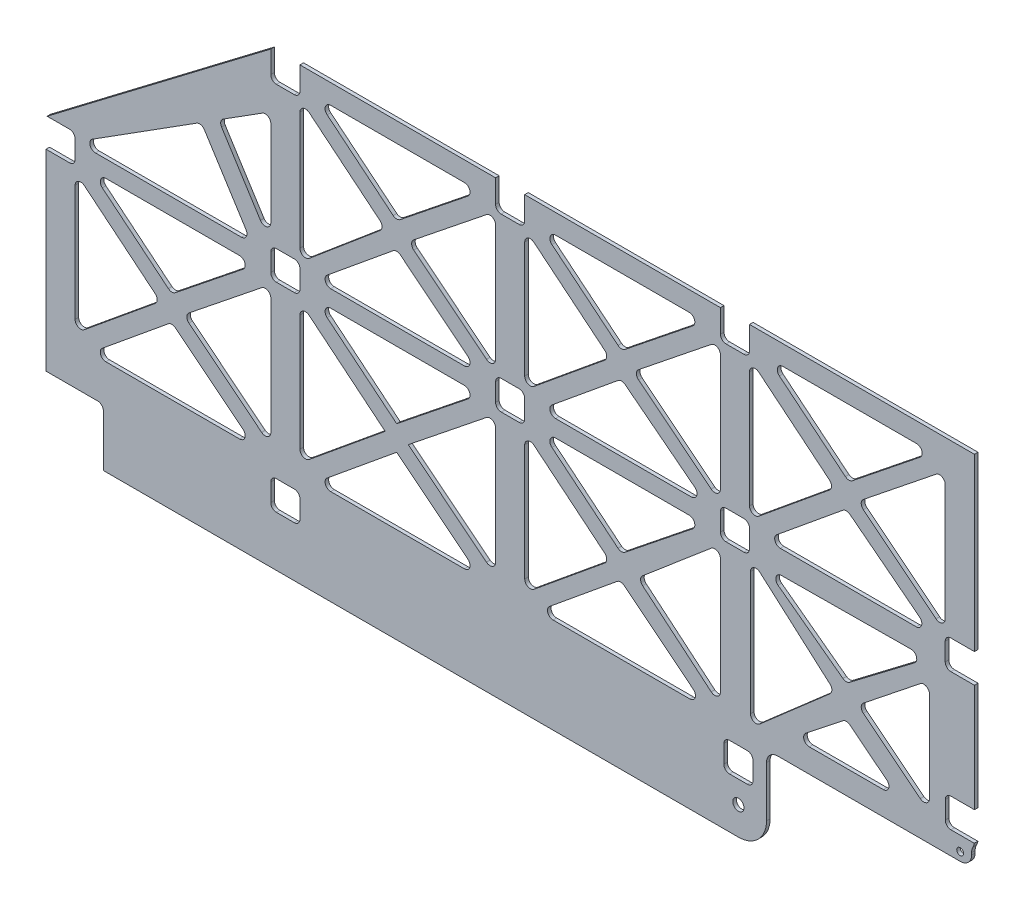
SolidWorks part; units mm, degrees
note: The reader was unsure of these and kept them because the rebuilt part matched: thickness of "Brida base1", "Chapa metálica1", "Chapa metálica23", "Chapa metálica27", "Chapa metálica32", "Chapa metálica33", "Chapa metálica34", "Chapa metálica35", "Chapa metálica36", "Chapa metálica37", "Chapa metálica38", "Chapa metálica39", "Chapa metálica40", "Chapa metálica41", "Chapa metálica42", "Chapa metálica43", "Chapa metálica44", "Chapa metálica45", "Chapa metálica46", "Chapa metálica47", "Chapa metálica48", "Chapa metálica49", "Chapa metálica50", "Chapa metálica51", "Chapa metálica52", "Chapa metálica53", "Chapa metálica54", "Chapa metálica55", "Chapa metálica56", "Chapa metálica57", "Chapa metálica58".
other "Elemento de detalle13"
other "Elemento de detalle19"
other "Carpeta de soldadura"
material "ASTM A36 Acero"
ref_plane "Alzado" through (0, 0, 0) normal (0, 0, 1) x (1, 0, 0)
ref_plane "Planta" through (0, 0, 0) normal (0, 1, 0) x (1, 0, 0)
ref_plane "Vista lateral" through (0, 0, 0) normal (1, 0, 0) x (0, 0, -1)
sketch "Croquis1" plane through (0, 0, 0) normal (0, 0, 1) x (1, 0, 0)
  line L1 (-634.7218, 129.9029) -> (1017.2782, 129.9029)
  line L2 (-634.7218, 129.9029) -> (-634.7218, -670.0971)
  line L3 (-634.7218, -670.0971) -> (1017.2782, -670.0971)
  line L4 (1017.2782, 129.9029) -> (1017.2782, -670.0971)
  dimension "D1" = 800
  dimension "D2" = 1652
base flange "Brida base1" sketch "Croquis1" thickness 6.35 reverse thickness direction no parameters "D1"=0.7366
ref_plane "Plano1" through (0, 0, 0) normal (0, 1, 0) x (1, 0, 0)
sketch "Croquis14" plane through (0, 0, -6.35) normal (0, 0, 1) x (1, 0, 0)
  line L0 (-634.7218, 129.9029) -> (-634.7218, -670.0971) construction
  line L1 (-634.7218, -670.0971) -> (1017.2782, -670.0971) construction
  line L2 (-634.7218, -174.1971) -> (-582.9218, -174.1971)
  line L3 (965.2782, -174.1971) -> (1028.4048, -174.1971)
  line L4 (-451.2573, -29.958) -> (-582.9218, -29.958) construction
  line L5 (-634.7218, -174.1971) -> (-634.7218, -225.9971)
  line L6 (-634.7218, -225.9971) -> (-582.9218, -225.9971)
  line L7 (-582.9218, -174.1971) -> (-582.9218, -225.9971)
  line L8 (1017.2782, 129.9029) -> (-634.7218, 129.9029) construction
  line L9 (-234.7218, -174.1971) -> (-182.9218, -174.1971)
  line L10 (-234.7218, -174.1971) -> (-234.7218, -225.9971)
  line L11 (1017.2782, 129.9029) -> (-634.7218, 129.9029) construction
  line L12 (-234.7218, -225.9971) -> (-182.9218, -225.9971)
  line L13 (-410.7218, 129.9029) -> (-410.7218, -670.0971) construction
  line L14 (-182.9218, -174.1971) -> (-182.9218, -225.9971)
  line L15 (165.2782, -174.1971) -> (217.0782, -174.1971)
  line L16 (165.2782, -174.1971) -> (165.2782, -225.9971)
  line L17 (165.2782, -225.9971) -> (217.0782, -225.9971)
  line L18 (217.0782, -174.1971) -> (217.0782, -225.9971)
  line L19 (565.2782, -174.1971) -> (617.0782, -174.1971)
  line L20 (565.2782, -174.1971) -> (565.2782, -225.9971)
  line L21 (565.2782, -225.9971) -> (617.0782, -225.9971)
  line L22 (617.0782, -174.1971) -> (617.0782, -225.9971)
  line L23 (165.2782, 130.8029) -> (217.0782, 130.8029)
  line L24 (589.2782, 129.9029) -> (589.2782, -670.0971) construction
  line L25 (89.2782, 129.9029) -> (89.2782, -670.0971) construction
  line L26 (565.2782, 130.8029) -> (617.0782, 130.8029)
  line L27 (565.2782, 130.8029) -> (565.2782, 79.0029)
  line L28 (565.2782, 79.0029) -> (617.0782, 79.0029)
  line L29 (617.0782, 130.8029) -> (617.0782, 79.0029)
  line L30 (-582.9218, 78.1029) -> (-582.9218, -138.0188) construction
  line L31 (-582.9218, -138.0188) -> (-451.2573, -29.958) construction
  line L32 (-451.2573, -29.958) -> (-582.9218, 78.1029) construction
  line L33 (789.2782, -227.6711) -> (789.2782, -337.0198) construction
  line L34 (809.8215, -360.2316) -> (937.2192, -360.2316) construction
  line L35 (417.7527, -360.2316) -> (789.2782, -360.2316) construction
  line L36 (-234.7218, 31.6626) -> (-234.7218, -174.0284)
  line L37 (-234.7218, -174.0284) -> (-327.6777, -27.1786)
  line L38 (965.2782, -174.1971) -> (965.2782, -225.9971)
  line L39 (215.2782, -200.0989) -> (315.2782, -200.0989) construction
  line L40 (617.0782, 78.1029) -> (617.0782, -170.9006)
  line L41 (965.2782, -225.9971) -> (1028.4048, -225.9971)
  line L42 (1028.4048, -174.1971) -> (1028.4048, -225.9971)
  line L43 (-634.7218, 129.9029) -> (-634.7218, -670.0971) construction
  line L44 (768.7748, -46.3989) -> (617.0782, 78.1029)
  line L45 (617.0782, -170.9006) -> (768.7748, -46.3989)
  line L46 (789.2782, -68.3814) -> (643.8962, -187.7006)
  line L47 (942.9042, -187.7006) -> (789.2782, -68.3814)
  line L48 (643.8962, -187.7006) -> (942.9042, -187.7006)
  line L49 (-327.6777, -27.1786) -> (-234.7218, 31.6626)
  line L50 (-268.9149, -187.7006) -> (-358.2681, -46.5423)
  line L51 (-358.2681, -46.5423) -> (-581.2671, -187.7006)
  line L52 (-234.7218, 79.0029) -> (-634.7218, -174.1971) construction
  line L53 (-634.7218, -174.1971) -> (-631.748, -174.0915) construction
  line L54 (937.2192, -258.7052) -> (937.2192, -461.7581)
  line L55 (-581.2671, -187.7006) -> (-268.9149, -187.7006)
  line L56 (694.6653, -467.8409) -> (883.8912, -467.8409)
  line L58 (789.2782, -467.8409) -> (789.2782, -392.9074) construction
  line L59 (789.2782, -68.3814) -> (789.2782, -360.2316) construction
  line L84 (165.2782, 130.8029) -> (165.2782, 79.0029)
  line L85 (165.2782, 79.0029) -> (217.0782, 79.0029)
  line L86 (217.0782, 130.8029) -> (217.0782, 79.0029)
  line L87 (-234.7218, 130.8029) -> (-182.9218, 130.8029)
  line L88 (-234.7218, 130.8029) -> (-234.7218, 79.0029)
  line L89 (-234.7218, 79.0029) -> (-182.9218, 79.0029)
  line L90 (-182.9218, 130.8029) -> (-182.9218, 79.0029)
  line L91 (-634.7218, 130.8029) -> (-582.9218, 130.8029)
  line L92 (-634.7218, 130.8029) -> (-634.7218, 79.0029)
  line L93 (-634.7218, 79.0029) -> (-582.9218, 79.0029)
  line L94 (-582.9218, 130.8029) -> (-582.9218, 79.0029)
  line L95 (-182.9218, 78.1029) -> (-182.9218, -174.0284)
  line L96 (-182.9218, -174.0284) -> (-31.2252, -46.3989)
  line L97 (-31.2252, -46.3989) -> (-182.9218, 78.1029)
  line L98 (-156.1038, 94.9029) -> (138.2639, 94.9029)
  line L99 (138.2639, 94.9029) -> (-10.7218, -24.4164)
  line L100 (-10.7218, -24.4164) -> (-156.1038, 94.9029)
  line L101 (165.2782, 78.1029) -> (165.2782, -170.9006)
  line L102 (165.2782, -170.9006) -> (9.8215, -46.3989)
  line L103 (9.8215, -46.3989) -> (165.2782, 78.1029)
  line L104 (-10.7218, -68.3814) -> (-156.1038, -187.7006)
  line L105 (138.2639, -187.7006) -> (-10.7218, -68.3814)
  line L106 (-156.1038, -187.7006) -> (138.2639, -187.7006)
  line L107 (-31.2252, -46.3989) -> (-182.9218, -46.3989) construction
  line L108 (217.0782, 78.1029) -> (217.0782, -170.9006)
  line L109 (217.0782, -170.9006) -> (368.7748, -46.3989)
  line L110 (368.7748, -46.3989) -> (217.0782, 78.1029)
  line L111 (243.8962, 94.9029) -> (538.2639, 94.9029)
  line L112 (538.2639, 94.9029) -> (389.2782, -24.4164)
  line L113 (389.2782, -24.4164) -> (243.8962, 94.9029)
  line L114 (565.2782, 78.1029) -> (565.2782, -170.9006)
  line L115 (565.2782, -170.9006) -> (409.8215, -46.3989)
  line L116 (409.8215, -46.3989) -> (565.2782, 78.1029)
  line L117 (389.2782, -68.3814) -> (243.8962, -187.7006)
  line L118 (542.9042, -187.7006) -> (389.2782, -68.3814)
  line L119 (243.8962, -187.7006) -> (542.9042, -187.7006)
  line L120 (368.7748, -46.3989) -> (217.0782, -46.3989) construction
  line L124 (648.5365, 94.9029) -> (942.9042, 94.9029)
  line L125 (942.9042, 94.9029) -> (793.9185, -24.4164)
  line L126 (793.9185, -24.4164) -> (648.5365, 94.9029)
  line L127 (965.2782, 78.1029) -> (965.2782, -170.9006)
  line L128 (965.2782, -170.9006) -> (809.8215, -46.3989)
  line L129 (809.8215, -46.3989) -> (965.2782, 78.1029)
  line L134 (-182.9218, -234.5006) -> (-182.9218, -483.5041)
  line L135 (-182.9218, -483.5041) -> (-31.2252, -359.0024)
  line L136 (-31.2252, -359.0024) -> (-182.9218, -234.5006)
  line L137 (-156.1038, -217.7006) -> (138.2639, -217.7006)
  line L138 (138.2639, -217.7006) -> (-10.7218, -337.0198)
  line L139 (-10.7218, -337.0198) -> (-156.1038, -217.7006)
  line L140 (165.2782, -234.5006) -> (165.2782, -483.5041)
  line L141 (165.2782, -483.5041) -> (9.8215, -359.0024)
  line L142 (9.8215, -359.0024) -> (165.2782, -234.5006)
  line L143 (-10.7218, -380.9849) -> (-156.1038, -500.3041)
  line L144 (138.2639, -500.3041) -> (-10.7218, -380.9849)
  line L145 (-156.1038, -500.3041) -> (138.2639, -500.3041)
  line L146 (-31.2252, -359.0024) -> (-182.9218, -359.0024) construction
  line L147 (217.0782, -234.5006) -> (217.0782, -483.5041)
  line L148 (217.0782, -483.5041) -> (368.7748, -359.0024)
  line L149 (368.7748, -359.0024) -> (217.0782, -234.5006)
  line L150 (243.8962, -217.7006) -> (538.2639, -217.7006)
  line L151 (538.2639, -217.7006) -> (389.2782, -337.0198)
  line L152 (389.2782, -337.0198) -> (243.8962, -217.7006)
  line L153 (565.2782, -235.1156) -> (565.2782, -484.1191)
  line L154 (565.2782, -484.1191) -> (417.7527, -360.2316)
  line L155 (417.7527, -360.2316) -> (565.2782, -235.1156)
  line L156 (387.6729, -378.8043) -> (239.634, -500.3041)
  line L157 (539.3812, -500.3041) -> (387.6729, -378.8043)
  line L158 (239.634, -500.3041) -> (539.3812, -500.3041)
  line L159 (368.7748, -359.0024) -> (217.0782, -359.0024) construction
  line L160 (618.7236, -228.0512) -> (618.7236, -491.1834)
  line L161 (618.7236, -491.1834) -> (768.7748, -360.2316)
  line L162 (768.7748, -360.2316) -> (618.7236, -228.0512)
  line L163 (643.8962, -228.8118) -> (934.6603, -226.5304)
  line L164 (934.6603, -226.5304) -> (789.2782, -337.0198)
  line L165 (789.2782, -337.0198) -> (643.8962, -228.8118)
  line L167 (937.2192, -461.7581) -> (809.8215, -360.2316)
  line L168 (809.8215, -360.2316) -> (937.2192, -258.7052)
  line L169 (789.2782, -392.9074) -> (694.6653, -467.8409)
  line L170 (883.8912, -467.8409) -> (789.2782, -392.9074)
  line L172 (768.7748, -360.2316) -> (615.7337, -360.2316) construction
  line L173 (-582.9218, -234.5006) -> (-582.9218, -483.5041)
  line L174 (-582.9218, -483.5041) -> (-431.2252, -359.0024)
  line L175 (-431.2252, -359.0024) -> (-582.9218, -234.5006)
  line L176 (-556.1038, -217.7006) -> (-261.7361, -217.7006)
  line L177 (-261.7361, -217.7006) -> (-410.7218, -337.0198)
  line L178 (-410.7218, -337.0198) -> (-556.1038, -217.7006)
  line L179 (-234.7218, -234.5006) -> (-234.7218, -483.5041)
  line L180 (-234.7218, -483.5041) -> (-390.1785, -359.0024)
  line L181 (-390.1785, -359.0024) -> (-234.7218, -234.5006)
  line L182 (-410.7218, -380.9849) -> (-556.1038, -500.3041)
  line L183 (-261.7361, -500.3041) -> (-410.7218, -380.9849)
  line L184 (-556.1038, -500.3041) -> (-261.7361, -500.3041)
  line L185 (-431.2252, -359.0024) -> (-582.9218, -359.0024) construction
  dimension "D21" = 30
  dimension "D3" = 0
  dimension "D4" = 2
  dimension "D5" = 51.8
  dimension "D6" = 51.8
  dimension "D7" = 51.8
  dimension "D8" = 304.1
  dimension "D9" = 2
  dimension "D10" = 2
  dimension "D11" = 2
  dimension "D12" = 4
  dimension "D13" = 2
  dimension "D14" = 224
  dimension "D15" = 40
  dimension "D16" = 400
  dimension "D18" = 400
  dimension "D19" = 400
  dimension "D29" = 1000
extrude "Cortar-Extruir1" cut sketch "Croquis14" along normal through all
ref_plane "Plano5" through (0, -200.0971, 0) normal (0, 1, 0) x (1, 0, 0)
ref_plane "Plano6" through (0, -40.0971, 0) normal (0, 1, 0) x (1, 0, 0)
ref_plane "Plano3" through (0, -420.0971, 0) normal (0, -1, 0) x (-1, 0, 0)
fillet "Redondeo1" radius 10 61 edges at (618.7236, -491.1834, -3.175) (617.0782, -225.9971, -3.175) (643.8962, -228.8118, -3.175) (934.6603, -226.5304, -3.175) (789.2782, -337.0198, -3.175) (789.2782, -392.9074, -3.175) (809.8215, -360.2316, -3.175) (-234.7218, -234.5006, -3.175) (-261.7361, -217.7006, -3.175) (-390.1785, -359.0024, -3.175) (-410.7218, -337.0198, -3.175) (-410.7218, -380.9849, -3.175) (-182.9218, -234.5006, -3.175) (243.8962, 94.9029, -3.175) (138.2639, -187.7006, -3.175) (-156.1038, -217.7006, -3.175) (-156.1038, -187.7006, -3.175) (-31.2252, -46.3989, -3.175) (-10.7218, -24.4164, -3.175) (-10.7218, -68.3814, -3.175) (165.2782, 78.1029, -3.175) (-182.9218, -483.5041, -3.175) (-261.7361, -500.3041, -3.175) (-156.1038, -500.3041, -3.175) (138.2639, -500.3041, -3.175) (243.8962, -217.7006, -3.175) (217.0782, -483.5041, -3.175) (565.2782, -484.1191, -3.175) (539.3812, -500.3041, -3.175) (368.7748, -359.0024, -3.175) (389.2782, -337.0198, -3.175) (387.6729, -378.8043, -3.175) (565.2782, -235.1156, -3.175) (538.2639, -217.7006, -3.175) (565.2782, -170.9006, -3.175) (243.8962, -187.7006, -3.175) (542.9042, -187.7006, -3.175) (368.7748, -46.3989, -3.175) (389.2782, -24.4164, -3.175) (409.8215, -46.3989, -3.175) (538.2639, 94.9029, -3.175) (565.2782, 78.1029, -3.175) (809.8215, -46.3989, -3.175) (965.2782, 78.1029, -3.175) (942.9042, 94.9029, -3.175) (-182.9218, 78.1029, -3.175) (617.0782, -170.9006, -3.175) (768.7748, -46.3989, -3.175) (789.2782, -68.3814, -3.175) (942.9042, -187.7006, -3.175) (643.8962, -187.7006, -3.175) (617.0782, -174.1971, -3.175) (565.2782, -174.1971, -3.175) (-581.2671, -187.7006, -3.175) (-268.9149, -187.7006, -3.175) (-234.7218, -174.0284, -3.175) (-327.6777, -27.1786, -3.175) (937.2192, -461.7581, -3.175) (937.2192, -258.7052, -3.175) (883.8912, -467.8409, -3.175) (694.6653, -467.8409, -3.175)
ref_plane "Plano7" through (0, -476.0971, 0) normal (0, -1, 0) x (-1, 0, 0)
ref_plane "Plano8" through (-410.7218, 0, 0) normal (-1, 0, 0) x (0, 0, 1)
ref_plane "Plano9" through (89.2782, 0, 0) normal (-1, 0, 0) x (0, 0, 1)
ref_plane "Plano10" through (591.1782, 0, 0) normal (-1, 0, 0) x (0, 0, 1)
fillet "Redondeo2" radius 10 18 edges at (-182.9218, -174.1971, -3.175) (-234.7218, -174.1971, -3.175) (-234.7218, -225.9971, -3.175) (165.2782, -225.9971, -3.175) (217.0782, -174.1971, -3.175) (165.2782, -174.1971, -3.175) (217.0782, -225.9971, -3.175) (-182.9218, -225.9971, -3.175) (-582.9218, -225.9971, -3.175) (-582.9218, -174.1971, -3.175) (-182.9218, 79.0029, -3.175) (-234.7218, 79.0029, -3.175) (217.0782, 79.0029, -3.175) (165.2782, 79.0029, -3.175) (617.0782, 79.0029, -3.175) (565.2782, 79.0029, -3.175) (965.2782, -225.9971, -3.175) (965.2782, -174.1971, -3.175)
ref_plane "Plano11" through (0, 104.0029, 0) normal (0, 1, 0) x (1, 0, 0)
sketch "Croquis15" plane through (0, 0, -6.35) normal (0, 0, -1) x (-1, 0, 0)
  line L0 (234.7218, 129.9029) -> (634.7218, -174.1971) construction
  line L1 (634.7218, -174.1971) -> (723.5953, -174.1971)
  line L2 (723.5953, -174.1971) -> (723.5953, 159.8909)
  line L3 (723.5953, 159.8909) -> (234.7218, 159.8909)
  line L4 (234.7218, 159.8909) -> (234.7218, 129.9029)
  line L5 (234.7218, 129.9029) -> (234.7218, 128.3578)
  line L6 (234.7218, 129.9029) -> (234.7218, 89.0029) construction
  line L7 (234.7218, 128.3578) -> (632.6894, -174.1971)
  line L9 (632.6894, -174.1971) -> (634.7218, -174.1971)
  line L10 (234.7218, 129.9029) -> (634.7218, 129.9029) construction
  dimension "D1" = 1.23
extrude "Cortar-Extruir2" cut sketch "Croquis15" against normal blind 10 contours L0 L5 L7 L9 | L4 L0 L1 L2 L3 normal cut yes
sketch "Croquis19" plane through (0, 0, 0) normal (0, 0, 1) x (1, 0, 0)
  line L1 (1017.2782, -670.0971) -> (647.2782, -670.0971)
  line L2 (1017.2782, -670.0971) -> (1017.2782, -510.0971)
  line L3 (1017.2782, -510.0971) -> (647.2782, -510.0971)
  line L4 (647.2782, -670.0971) -> (647.2782, -510.0971)
  line L5 (1017.2782, -510.0971) -> (1012.2782, -510.0971)
  line L6 (1017.2782, -510.0971) -> (1017.2782, -480.0971)
  line L7 (1017.2782, -480.0971) -> (1012.2782, -480.0971)
  line L9 (1012.2782, -510.0971) -> (1012.2782, -480.0971)
  dimension "D1" = 160
  dimension "D2" = 370
  dimension "D3" = 30
  dimension "D4" = 5
extrude "Cortar-Extruir3" cut sketch "Croquis19" against normal blind 10 contours L4 L1 L2 L3 | L5 L9 L7 L6 normal cut yes
fillet "Redondeo4" radius 50 1 edges at (647.2782, -670.0971, -3.175)
fillet "Redondeo5" radius 20 3 edges at (647.2782, -510.0971, -3.175) (1017.2782, -480.0971, -3.175)
fillet "Redondeo6" radius 50 1 edges at (-634.7218, -670.0971, -3.175)
fillet "Redondeo7" radius 20 1 edges at (1012.2782, -480.0971, -3.175)
sketch "Croquis20" plane through (0, 0, 0) normal (0, 0, 1) x (1, 0, 0)
  line L0 (966.4782, -510.0971) -> (966.4782, -495.0971) construction
  line L1 (992.2782, -510.0971) -> (667.2782, -510.0971) construction
  line L2 (966.4782, -495.0971) -> (1017.2782, -495.0971) construction
  line L3 (597.2782, -670.0971) -> (597.2782, -620.0971) construction
  line L4 (597.2782, -620.0971) -> (632.6336, -655.4525) construction
  line L5 (1017.2782, -466.8684) -> (1017.2782, -225.9971) construction
  line L7 (991.8782, -488.9971) -> (991.8782, -501.1971) construction
  arc A2 (597.2782, -670.0971) -> (647.2782, -620.0971) centre (597.2782, -620.0971) ccw construction
  circle A3 centre (597.2782, -620.0971) radius 10
  circle A5 centre (991.8782, -495.0971) radius 6.1
  dimension "D1" = 20
  dimension "D4" = 12.2
  dimension "D2" = 45
  dimension "D3" = 15
  dimension "D5" = 20.4
extrude "Cortar-Extruir4" cut sketch "Croquis20" against normal blind 10 normal cut yes
sketch "Croquis21" plane through (0, 0, 0) normal (0, 0, 1) x (1, 0, 0)
  line L0 (-584.7218, -670.0971) -> (597.2782, -670.0971) construction
  line L1 (571.3782, -528.7971) -> (623.1782, -528.7971)
  line L2 (571.3782, -528.7971) -> (571.3782, -580.5971)
  line L3 (571.3782, -580.5971) -> (623.1782, -580.5971)
  line L4 (623.1782, -528.7971) -> (623.1782, -580.5971)
  line L5 (647.2782, -530.0971) -> (647.2782, -620.0971) construction
  line L6 (1017.2782, -466.8684) -> (1017.2782, -225.9971) construction
  line L7 (1017.2782, -469.6371) -> (965.4782, -469.6371)
  line L8 (1017.2782, -469.6371) -> (1017.2782, -417.8371)
  line L9 (1017.2782, -417.8371) -> (965.4782, -417.8371)
  line L11 (965.4782, -469.6371) -> (965.4782, -417.8371)
  line L12 (992.2782, -510.0971) -> (667.2782, -510.0971) construction
  line L13 (-234.7218, -528.7971) -> (-182.9218, -528.7971)
  line L14 (-234.7218, -528.7971) -> (-234.7218, -580.5971)
  line L15 (-234.7218, -580.5971) -> (-182.9218, -580.5971)
  line L16 (-182.9218, -528.7971) -> (-182.9218, -580.5971)
  line L17 (-208.8218, -528.7971) -> (-208.8218, -225.9971) construction
  line L18 (-224.7218, -225.9971) -> (-192.9218, -225.9971) construction
  line L19 (-634.7218, -567.9971) -> (-532.6218, -567.9971)
  line L20 (-634.7218, -567.9971) -> (-634.7218, -670.0971)
  line L21 (-634.7218, -670.0971) -> (-532.6218, -670.0971)
  line L22 (-532.6218, -567.9971) -> (-532.6218, -670.0971)
  dimension "D1" = 89.5
  dimension "D2" = 51.8
  dimension "D3" = 51.8
  dimension "D4" = 24.1
  dimension "D5" = 51.8
  dimension "D6" = 51.8
  dimension "D7" = 40.46
  dimension "D8" = 2
  dimension "D10" = 102.1
  dimension "D9" = 102.1
extrude "Cortar-Extruir5" cut sketch "Croquis21" against normal blind 10 normal cut yes
fillet "Redondeo8" radius 10 11 edges at (623.1782, -580.5971, -3.175) (623.1782, -528.7971, -3.175) (571.3782, -580.5971, -3.175) (571.3782, -528.7971, -3.175) (-532.6218, -567.9971, -3.175) (-234.7218, -580.5971, -3.175) (-182.9218, -580.5971, -3.175) (-182.9218, -528.7971, -3.175) (-234.7218, -528.7971, -3.175) (965.4782, -417.8371, -3.175) (965.4782, -469.6371, -3.175)
hole_wizard "Taladro de margen para 1/41" [suppressed] positions "Croquis17" profile "Croquis18" hole size "1/4" standard "Ansi Inch"
sketch "Croquis17" plane through (0, 0, -6.35) normal (0, 0, -1) x (-1, 0, 0)
  line L0 (-965.2783, -215.9583) -> (-617.0782, -501.7695) construction
  line L2 (-1017.2782, -417.8371) -> (-1017.2782, -225.9971) construction
  line L3 (-1017.2782, 129.9029) -> (-617.0782, 129.9029) construction
  line L6 (-591.1782, -174.1971) -> (-591.1782, -669.7411) construction
  line L9 (-575.2782, -174.1971) -> (-607.0782, -174.1971) construction
  line L10 (-217.0782, -215.9583) -> (-565.2782, -501.7695) construction
  line L11 (208.8218, -174.1971) -> (208.8218, -563.5848) construction
  line L12 (224.7218, -174.1971) -> (192.9218, -174.1971) construction
  line L15 (-165.2782, -215.9971) -> (184.1077, -502.743) construction
  line L17 (582.9218, -215.9971) -> (233.5358, -502.743) construction
  line L18 (234.7218, -202.0738) -> (-965.2782, -202.0738) construction
  line L22 (592.9218, -174.1971) -> (234.7218, 89.0029) construction
  line L23 (-165.2782, -188.1504) -> (184.1077, 98.5954) construction
  line L24 (-217.0782, -188.1893) -> (-565.2782, 97.622) construction
  line L25 (-965.2783, -188.1893) -> (-617.0782, 97.622) construction
  line L26 (3.4925, 104.0029) -> (-3.4925, 104.0029) construction
  line L27 (-617.0782, 129.9029) -> (-617.0782, 89.0029) construction
  arc A0 (-975.2782, -225.9971) -> (-965.2782, -215.9971) centre (-975.2782, -215.9971) ccw construction
  point P0 (-944.3982, -233.0971)
  point P20 (-878.6971, -287.0263)
  point P22 (-812.9959, -340.9555)
  point P24 (-747.2947, -394.8846)
  point P26 (-681.5935, -448.8138)
  point P28 (-615.8923, -502.743)
  point P45 (-144.3982, -233.0971)
  point P46 (-78.6971, -287.0263)
  point P47 (-12.9959, -340.9555)
  point P48 (52.7053, -394.8846)
  point P49 (118.4065, -448.8138)
  point P50 (184.1077, -502.743)
  point P58 (-566.4642, -502.743)
  point P59 (-500.763, -448.8138)
  point P60 (-435.0618, -394.8846)
  point P61 (-369.3606, -340.9555)
  point P62 (-303.6594, -287.0263)
  point P63 (-237.9582, -233.0971)
  point P79 (299.237, -448.8138)
  point P80 (364.9382, -394.8846)
  point P81 (430.6394, -340.9555)
  point P82 (496.3406, -287.0263)
  point P83 (562.0418, -233.0971)
  point P85 (233.5358, -502.743)
  point P103 (561.7086, -151.2622)
  point P104 (-237.9582, -171.0504)
  point P105 (-144.3982, -171.0504)
  point P106 (-944.3982, -171.0504)
  point P107 (460.6336, -76.9938)
  point P108 (361.7516, -4.3368)
  point P110 (273.454, 60.543)
  point P112 (-391.1782, -45.2837)
  point P118 (9.4147, -44.7775)
  point P122 (-791.1783, -45.2837)
  point P130 (-991.5269, 106.7021)
  point P134 (-991.5269, -9.8578)
  point P136 (-991.5269, -117.7161)
  point P138 (-991.5269, -287.0263)
  point P140 (-991.5269, -394.8846)
  point P142 (-921.6699, -488.9971)
  point P150 (-615.8923, -639.6504)
  point P152 (-500.763, -639.6504)
  point P154 (-369.3606, -639.6504)
  point P156 (-237.9582, -639.6504)
  point P158 (-144.3982, -639.6504)
  point P160 (-12.9959, -639.6504)
  point P162 (118.4065, -639.6504)
  point P164 (233.5358, -639.6504)
  point P166 (364.9382, -639.6504)
  point P168 (496.3406, -639.6504)
  point P170 (610.1291, -287.0263)
  point P172 (610.1291, -394.8846)
  point P174 (610.1291, -502.743)
  point P192 (-878.6971, 106.7021)
  point P194 (-747.2947, 106.7021)
  point P196 (-649.2897, 106.7021)
  point P198 (-591.1782, -53.6679)
  point P200 (-591.1782, -355.2986)
  point P202 (-189.8489, -53.6679)
  point P204 (-189.8489, -355.2986)
  point P206 (208.8218, -355.2986)
  point P208 (208.8218, -53.6679)
  point P210 (420.4568, -202.3712)
  point P212 (-394.0946, -202.0738)
  point P214 (20.3895, -202.0738)
  point P216 (-791.7591, -202.0738)
  point P218 (-500.763, 106.7021)
  point P220 (-365.2782, 106.7021)
  point P222 (-237.9582, 104.0029)
  point P226 (-144.3982, 104.0029)
  point P228 (11.8701, 106.7021)
  point P230 (157.194, 106.7021)
  point P232 (-791.7591, -488.9971)
  point P234 (-396.2353, -488.9971)
  point P236 (21.2259, -488.9971)
  point P238 (421.2932, -488.9971)
  dimension "D1" = 50.62
  dimension "D2" = 72.88
  dimension "D3" = 363
  dimension "D4" = 85
  dimension "D5" = 85
  dimension "D6" = 85
  dimension "D7" = 85
  dimension "D8" = 85
  dimension "D10" = 85
  dimension "D9" = 2
sketch "Croquis18" plane through (944.3982, -233.0971, -6.35) normal (1, 0, 0) x (0, 1, 0)
  line L0 (0, 0) -> (0, 6.35)
  line L1 (0, 6.35) -> (3.3782, 6.35)
  line L2 (3.3782, 6.35) -> (3.3782, 0)
  line L5 (3.3782, 0) -> (0, 0)
  line L11 (0, -6.35) -> (0, 107.95) construction
  dimension "Diámetro de taladro hasta el siguiente" = 6.7564
  dimension "Profundidad de taladro hasta el siguiente" = 6.35
sketch "Líneas de pliegue1" [suppressed] plane through (0, 0, 0) normal (0, 1, 0) x (1, 0, 0)
sketch "Cuadro delimitador1" [suppressed] plane through (0, 0, 0) normal (0, 1, 0) x (1, 0, 0)
sheet metal parameters "Chapa metálica1" thickness 6.35 parameters "D1"=0.7366
flat pattern "Chapa desplegada1" [suppressed]
sketch "Líneas de pliegue2" plane through (0, 0, 0) normal (0, 1, 0) x (1, 0, 0)
sketch3d "Cuadro delimitador2" [suppressed]
  line L0 (-634.7218, -670.0971, 0) -> (1037.2782, -670.0971, 0) construction
  line L1 (-634.7218, 129.9029, 0) -> (1037.2782, 129.9029, 0) construction
  line L2 (-634.7218, -670.0971, 0) -> (-634.7218, 129.9029, 0) construction
  line L3 (1037.2782, -670.0971, 0) -> (1037.2782, 129.9029, 0) construction
sheet metal parameters "Chapa metálica23" thickness 6.35 parameters "D1"=0.7366, "D7"=12.7
flat pattern "Chapa desplegada1"
sketch "Líneas de pliegue2" plane through (0, 0, 0) normal (0, 1, 0) x (1, 0, 0)
sketch3d "Cuadro delimitador2" [suppressed]
  line L0 (-634.7218, -370.0971, 0) -> (1165.2782, -370.0971, 0) construction
  line L1 (-634.7218, 129.9029, 0) -> (1165.2782, 129.9029, 0) construction
  line L2 (-634.7218, -370.0971, 0) -> (-634.7218, 129.9029, 0) construction
  line L3 (1165.2782, -370.0971, 0) -> (1165.2782, 129.9029, 0) construction
sheet metal parameters "Chapa metálica27" thickness 6.35 parameters "D1"=0.7366, "D7"=12.7
flat pattern "Chapa desplegada1"
sketch "Líneas de pliegue2" plane through (0, 0, 0) normal (0, 1, 0) x (1, 0, 0)
sketch3d "Cuadro delimitador2" [suppressed]
  line L0 (-634.7218, -670.0971, 0) -> (1165.2782, -670.0971, 0) construction
  line L1 (-634.7218, 129.9029, 0) -> (1165.2782, 129.9029, 0) construction
  line L2 (-634.7218, -670.0971, 0) -> (-634.7218, 129.9029, 0) construction
  line L3 (1165.2782, -670.0971, 0) -> (1165.2782, 129.9029, 0) construction
sheet metal parameters "Chapa metálica29" thickness 12.7 parameters "D1"=0.7366
flat pattern "Chapa desplegada29"
sketch "Líneas de pliegue4" plane through (0, 0, 0) normal (0, 1, 0) x (1, 0, 0)
sketch3d "Cuadro delimitador4" [suppressed]
  line L0 (-119.0982, -238.1302, 0) -> (165.2782, -238.1302, 0) construction
  line L1 (-119.0982, -2.2285, 0) -> (165.2782, -2.2285, 0) construction
  line L2 (-119.0982, -238.1302, 0) -> (-119.0982, -2.2285, 0) construction
  line L3 (165.2782, -238.1302, 0) -> (165.2782, -2.2285, 0) construction
sheet metal parameters "Chapa metálica30" thickness 12.7 parameters "D1"=0.7366
flat pattern "Chapa desplegada30"
sketch "Líneas de pliegue5" plane through (0, 0, 0) normal (0, 1, 0) x (1, 0, 0)
sketch3d "Cuadro delimitador5" [suppressed]
  line L0 (-485.077, -310.0971, 0) -> (205.2782, -310.0971, 0) construction
  line L1 (-485.077, -211.7375, 0) -> (205.2782, -211.7375, 0) construction
  line L2 (-485.077, -310.0971, 0) -> (-485.077, -211.7375, 0) construction
  line L3 (205.2782, -310.0971, 0) -> (205.2782, -211.7375, 0) construction
sheet metal parameters "Chapa metálica31" thickness 12.7 parameters "D1"=0.7366
flat pattern "Chapa desplegada31"
sketch "Líneas de pliegue6" plane through (0, 0, 0) normal (0, 1, 0) x (1, 0, 0)
sketch3d "Cuadro delimitador6" [suppressed]
  line L0 (-484.7218, -29.6275, 0) -> (205.2782, -29.6275, 0) construction
  line L1 (-484.7218, 69.9029, 0) -> (205.2782, 69.9029, 0) construction
  line L2 (-484.7218, -29.6275, 0) -> (-484.7218, 69.9029, 0) construction
  line L3 (205.2782, -29.6275, 0) -> (205.2782, 69.9029, 0) construction
sheet metal parameters "Chapa metálica32" thickness 6.35 parameters "D1"=0.7366
flat pattern "Chapa desplegada1"
sketch "Líneas de pliegue7" plane through (0, 0, 0) normal (0, 1, 0) x (1, 0, 0)
sketch3d "Cuadro delimitador7" [suppressed]
  line L0 (-634.7218, -670.0971, 0) -> (1165.2782, -670.0971, 0) construction
  line L1 (-634.7218, 129.9029, 0) -> (1165.2782, 129.9029, 0) construction
  line L2 (-634.7218, -670.0971, 0) -> (-634.7218, 129.9029, 0) construction
  line L3 (1165.2782, -670.0971, 0) -> (1165.2782, 129.9029, 0) construction
sheet metal parameters "Chapa metálica33" thickness 6.35 parameters "D1"=0.7366
flat pattern "Chapa desplegada33"
sketch "Líneas de pliegue8" plane through (0, 0, 0) normal (0, 1, 0) x (1, 0, 0)
sketch "Cuadro delimitador8" [suppressed] plane through (0, 0, 0) normal (0, 1, 0) x (1, 0, 0)
sheet metal parameters "Chapa metálica34" thickness 6.35 parameters "D1"=0.7366
flat pattern "Chapa desplegada34"
sketch "Líneas de pliegue9" plane through (0, 0, 0) normal (0, 1, 0) x (1, 0, 0)
sketch "Cuadro delimitador9" [suppressed] plane through (0, 0, 0) normal (0, 1, 0) x (1, 0, 0)
sheet metal parameters "Chapa metálica35" thickness 6.35 parameters "D1"=0.7366
flat pattern "Chapa desplegada1"
sketch "Líneas de pliegue10" plane through (0, 0, 0) normal (0, 1, 0) x (1, 0, 0)
sketch3d "Cuadro delimitador10" [suppressed]
  line L0 (-634.7218, -670.0971, 0) -> (1017.2782, -670.0971, 0) construction
  line L1 (-634.7218, 129.9029, 0) -> (1017.2782, 129.9029, 0) construction
  line L2 (-634.7218, -670.0971, 0) -> (-634.7218, 129.9029, 0) construction
  line L3 (1017.2782, -670.0971, 0) -> (1017.2782, 129.9029, 0) construction
sheet metal parameters "Chapa metálica36" thickness 6.35 parameters "D1"=0.7366
flat pattern "Chapa desplegada36"
sketch "Líneas de pliegue11" plane through (0, 0, 0) normal (0, 1, 0) x (1, 0, 0)
sketch "Cuadro delimitador11" [suppressed] plane through (0, 0, 0) normal (0, 1, 0) x (1, 0, 0)
sheet metal parameters "Chapa metálica37" thickness 6.35 parameters "D1"=0.7366
flat pattern "Chapa desplegada1"
sketch "Líneas de pliegue12" plane through (0, 0, 0) normal (0, 1, 0) x (1, 0, 0)
sketch "Cuadro delimitador12" [suppressed] plane through (0, 0, 0) normal (0, 1, 0) x (1, 0, 0)
sheet metal parameters "Chapa metálica38" thickness 6.35 parameters "D1"=0.7366
flat pattern "Chapa desplegada38"
sketch "Líneas de pliegue13" plane through (0, 0, 0) normal (0, 1, 0) x (1, 0, 0)
sketch "Cuadro delimitador13" [suppressed] plane through (0, 0, 0) normal (0, 1, 0) x (1, 0, 0)
sheet metal parameters "Chapa metálica39" thickness 6.35 parameters "D1"=0.7366
flat pattern "Chapa desplegada39"
sketch "Líneas de pliegue14" plane through (0, 0, 0) normal (0, 1, 0) x (1, 0, 0)
sketch "Cuadro delimitador14" [suppressed] plane through (0, 0, 0) normal (0, 1, 0) x (1, 0, 0)
sheet metal parameters "Chapa metálica40" thickness 6.35 parameters "D1"=0.7366
flat pattern "Chapa desplegada40"
sketch "Líneas de pliegue15" plane through (0, 0, 0) normal (0, 1, 0) x (1, 0, 0)
sketch "Cuadro delimitador15" [suppressed] plane through (0, 0, 0) normal (0, 1, 0) x (1, 0, 0)
sheet metal parameters "Chapa metálica41" thickness 6.35 parameters "D1"=0.7366
flat pattern "Chapa desplegada41"
sketch "Líneas de pliegue16" plane through (0, 0, 0) normal (0, 1, 0) x (1, 0, 0)
sketch "Cuadro delimitador16" [suppressed] plane through (0, 0, 0) normal (0, 1, 0) x (1, 0, 0)
sheet metal parameters "Chapa metálica42" thickness 6.35 parameters "D1"=0.7366
flat pattern "Chapa desplegada42"
sketch "Líneas de pliegue17" plane through (0, 0, 0) normal (0, 1, 0) x (1, 0, 0)
sketch "Cuadro delimitador17" [suppressed] plane through (0, 0, 0) normal (0, 1, 0) x (1, 0, 0)
sheet metal parameters "Chapa metálica43" thickness 6.35 parameters "D1"=0.7366
flat pattern "Chapa desplegada43"
sketch "Líneas de pliegue18" plane through (0, 0, 0) normal (0, 1, 0) x (1, 0, 0)
sketch "Cuadro delimitador18" [suppressed] plane through (0, 0, 0) normal (0, 1, 0) x (1, 0, 0)
sheet metal parameters "Chapa metálica44" thickness 6.35 parameters "D1"=0.7366
flat pattern "Chapa desplegada44"
sketch "Líneas de pliegue19" plane through (0, 0, 0) normal (0, 1, 0) x (1, 0, 0)
sketch "Cuadro delimitador19" [suppressed] plane through (0, 0, 0) normal (0, 1, 0) x (1, 0, 0)
sheet metal parameters "Chapa metálica45" thickness 6.35 parameters "D1"=0.7366
flat pattern "Chapa desplegada45"
sketch "Líneas de pliegue20" plane through (0, 0, 0) normal (0, 1, 0) x (1, 0, 0)
sketch "Cuadro delimitador20" [suppressed] plane through (0, 0, 0) normal (0, 1, 0) x (1, 0, 0)
sheet metal parameters "Chapa metálica46" thickness 6.35 parameters "D1"=0.7366
flat pattern "Chapa desplegada46"
sketch "Líneas de pliegue21" plane through (0, 0, 0) normal (0, 1, 0) x (1, 0, 0)
sketch "Cuadro delimitador21" [suppressed] plane through (0, 0, 0) normal (0, 1, 0) x (1, 0, 0)
sheet metal parameters "Chapa metálica47" thickness 6.35 parameters "D1"=0.7366
flat pattern "Chapa desplegada47"
sketch "Líneas de pliegue22" plane through (0, 0, 0) normal (0, 1, 0) x (1, 0, 0)
sketch3d "Cuadro delimitador22" [suppressed]
  line L0 (-11.8337, -225.9971, 0) -> (-8.8218, -225.9971, 0) construction
  line L1 (-11.8337, -223.418, 0) -> (-8.8218, -223.418, 0) construction
  line L2 (-11.8337, -225.9971, 0) -> (-11.8337, -223.418, 0) construction
  line L3 (-8.8218, -225.9971, 0) -> (-8.8218, -223.418, 0) construction
sheet metal parameters "Chapa metálica48" thickness 6.35 parameters "D1"=0.7366
flat pattern "Chapa desplegada48"
sketch "Líneas de pliegue23" plane through (0, 0, 0) normal (0, 1, 0) x (1, 0, 0)
sketch "Cuadro delimitador23" [suppressed] plane through (0, 0, 0) normal (0, 1, 0) x (1, 0, 0)
sheet metal parameters "Chapa metálica49" thickness 6.35 parameters "D1"=0.7366
flat pattern "Chapa desplegada49"
sketch "Líneas de pliegue24" plane through (0, 0, 0) normal (0, 1, 0) x (1, 0, 0)
sketch "Cuadro delimitador24" [suppressed] plane through (0, 0, 0) normal (0, 1, 0) x (1, 0, 0)
sheet metal parameters "Chapa metálica50" thickness 6.35 parameters "D1"=0.7366
flat pattern "Chapa desplegada50"
sketch "Líneas de pliegue25" plane through (0, 0, 0) normal (0, 1, 0) x (1, 0, 0)
sketch "Cuadro delimitador25" [suppressed] plane through (0, 0, 0) normal (0, 1, 0) x (1, 0, 0)
sheet metal parameters "Chapa metálica51" thickness 6.35 parameters "D1"=0.7366
flat pattern "Chapa desplegada51"
sketch "Líneas de pliegue26" plane through (0, 0, 0) normal (0, 1, 0) x (1, 0, 0)
sketch3d "Cuadro delimitador26" [suppressed]
  line L0 (1017.0782, -174.1971, 0) -> (1017.0782, -225.9971, 0) construction
  line L1 (965.2782, -174.1971, 0) -> (965.2782, -225.9971, 0) construction
  line L2 (1017.0782, -174.1971, 0) -> (965.2782, -174.1971, 0) construction
  line L3 (1017.0782, -225.9971, 0) -> (965.2782, -225.9971, 0) construction
sheet metal parameters "Chapa metálica52" thickness 6.35 parameters "D1"=0.7366
flat pattern "Chapa desplegada52"
sketch "Líneas de pliegue27" plane through (0, 0, 0) normal (0, 1, 0) x (1, 0, 0)
sketch3d "Cuadro delimitador27" [suppressed]
  line L0 (565.2782, -225.9971, 0) -> (617.0782, -225.9971, 0) construction
  line L1 (565.2782, -174.1971, 0) -> (617.0782, -174.1971, 0) construction
  line L2 (565.2782, -225.9971, 0) -> (565.2782, -174.1971, 0) construction
  line L3 (617.0782, -225.9971, 0) -> (617.0782, -174.1971, 0) construction
sheet metal parameters "Chapa metálica53" thickness 6.35 parameters "D1"=0.7366
flat pattern "Chapa desplegada53"
sketch "Líneas de pliegue28" plane through (0, 0, 0) normal (0, 1, 0) x (1, 0, 0)
sketch3d "Cuadro delimitador28" [suppressed]
  line L0 (-634.7218, 79.0029, 0) -> (-582.9218, 79.0029, 0) construction
  line L1 (-634.7218, 129.9029, 0) -> (-582.9218, 129.9029, 0) construction
  line L2 (-634.7218, 79.0029, 0) -> (-634.7218, 129.9029, 0) construction
  line L3 (-582.9218, 79.0029, 0) -> (-582.9218, 129.9029, 0) construction
sheet metal parameters "Chapa metálica54" thickness 6.35 parameters "D1"=0.7366
flat pattern "Chapa desplegada1"
sketch "Líneas de pliegue10" plane through (0, 0, 0) normal (0, 1, 0) x (1, 0, 0)
sketch3d "Cuadro delimitador10" [suppressed]
  line L0 (-634.7218, -670.0971, 0) -> (1017.2782, -670.0971, 0) construction
  line L1 (-634.7218, 129.9029, 0) -> (1017.2782, 129.9029, 0) construction
  line L2 (-634.7218, -670.0971, 0) -> (-634.7218, 129.9029, 0) construction
  line L3 (1017.2782, -670.0971, 0) -> (1017.2782, 129.9029, 0) construction
sheet metal parameters "Chapa metálica55" thickness 6.35 parameters "D1"=0.7366
flat pattern "Chapa desplegada1"
sketch "Líneas de pliegue10" plane through (0, 0, 0) normal (0, 1, 0) x (1, 0, 0)
sketch3d "Cuadro delimitador10" [suppressed]
  line L0 (-634.7218, -670.0971, 0) -> (1017.2782, -670.0971, 0) construction
  line L1 (-634.7218, 129.9029, 0) -> (1017.2782, 129.9029, 0) construction
  line L2 (-634.7218, -670.0971, 0) -> (-634.7218, 129.9029, 0) construction
  line L3 (1017.2782, -670.0971, 0) -> (1017.2782, 129.9029, 0) construction
sheet metal parameters "Chapa metálica56" thickness 6.35 parameters "D1"=0.7366
flat pattern "Chapa desplegada1"
sketch "Líneas de pliegue10" plane through (0, 0, 0) normal (0, 1, 0) x (1, 0, 0)
sketch3d "Cuadro delimitador10" [suppressed]
  line L0 (-634.7218, -670.0971, 0) -> (1017.2782, -670.0971, 0) construction
  line L1 (-634.7218, 129.9029, 0) -> (1017.2782, 129.9029, 0) construction
  line L2 (-634.7218, -670.0971, 0) -> (-634.7218, 129.9029, 0) construction
  line L3 (1017.2782, -670.0971, 0) -> (1017.2782, 129.9029, 0) construction
sheet metal parameters "Chapa metálica57" thickness 6.35 parameters "D1"=0.7366
flat pattern "Chapa desplegada1"
sketch "Líneas de pliegue10" plane through (0, 0, 0) normal (0, 1, 0) x (1, 0, 0)
sketch3d "Cuadro delimitador10" [suppressed]
  line L0 (-634.7218, -670.0971, 0) -> (1017.2782, -670.0971, 0) construction
  line L1 (-634.7218, 129.9029, 0) -> (1017.2782, 129.9029, 0) construction
  line L2 (-634.7218, -670.0971, 0) -> (-634.7218, 129.9029, 0) construction
  line L3 (1017.2782, -670.0971, 0) -> (1017.2782, 129.9029, 0) construction
sheet metal parameters "Chapa metálica58" thickness 6.35 parameters "D1"=0.7366
flat pattern "Chapa desplegada1"
sketch "Líneas de pliegue10" plane through (0, 0, 0) normal (0, 1, 0) x (1, 0, 0)
sketch3d "Cuadro delimitador10" [suppressed]
  line L0 (-634.7218, -670.0971, 0) -> (1017.2782, -670.0971, 0) construction
  line L1 (-634.7218, 129.9029, 0) -> (1017.2782, 129.9029, 0) construction
  line L2 (-634.7218, -670.0971, 0) -> (-634.7218, 129.9029, 0) construction
  line L3 (1017.2782, -670.0971, 0) -> (1017.2782, 129.9029, 0) construction
